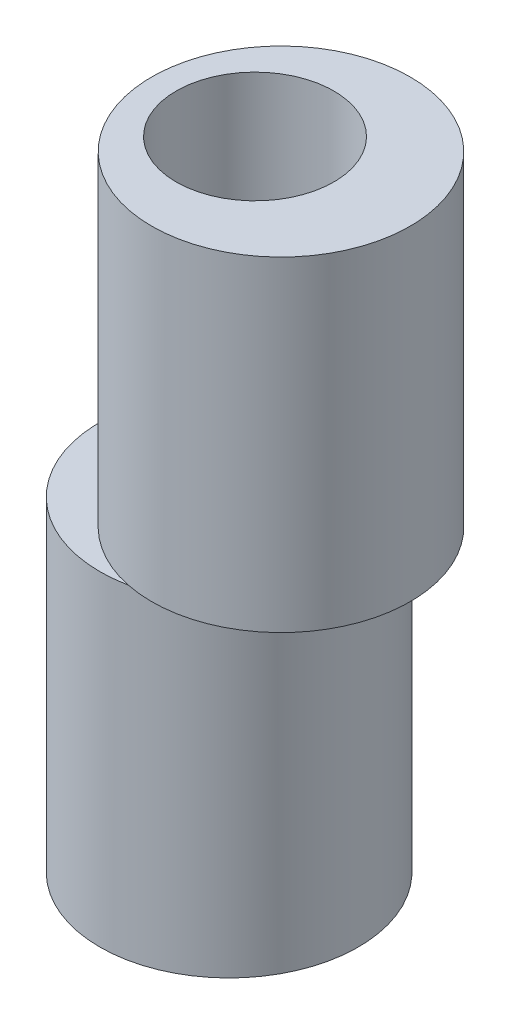
SolidWorks part; units mm, degrees
ref_plane "Front Plane" through (0, 0, 0) normal (0, 0, 1) x (1, 0, 0)
ref_plane "Top Plane" through (0, 0, 0) normal (0, 1, 0) x (1, 0, 0)
ref_plane "Right Plane" through (0, 0, 0) normal (1, 0, 0) x (0, 0, -1)
sketch "Sketch1" plane through (0, 0, 0) normal (0, 1, 0) x (1, 0, 0)
  line L0 (-1.6, 0.0042) -> (0, 0) construction
  circle A0 centre (0, 0) radius 3.975
  circle A1 centre (-1.6, 0.0042) radius 3.975
  circle A2 centre (-0.8, 0.0021) radius 2.425
  dimension "D1" = 7.95
  dimension "D2" = 7.95
  dimension "D3" = 4.85
extrude "Boss-Extrude1" add sketch "Sketch1" along normal blind 10 contours A0
sketch "Sketch2" plane through (0, 0, 0) normal (0, 1, 0) x (1, 0, 0)
  circle A0 centre (-1.6, 0.0042) radius 3.975
extrude "Boss-Extrude2" add sketch "Sketch2" against normal blind 10
sketch "Sketch4" plane through (0, 0, 0) normal (0, 1, 0) x (1, 0, 0)
  circle A0 centre (-0.8, 0.0021) radius 2.425
extrude "Cut-Extrude1" cut sketch "Sketch4" against normal blind 10 and the other way blind 10
